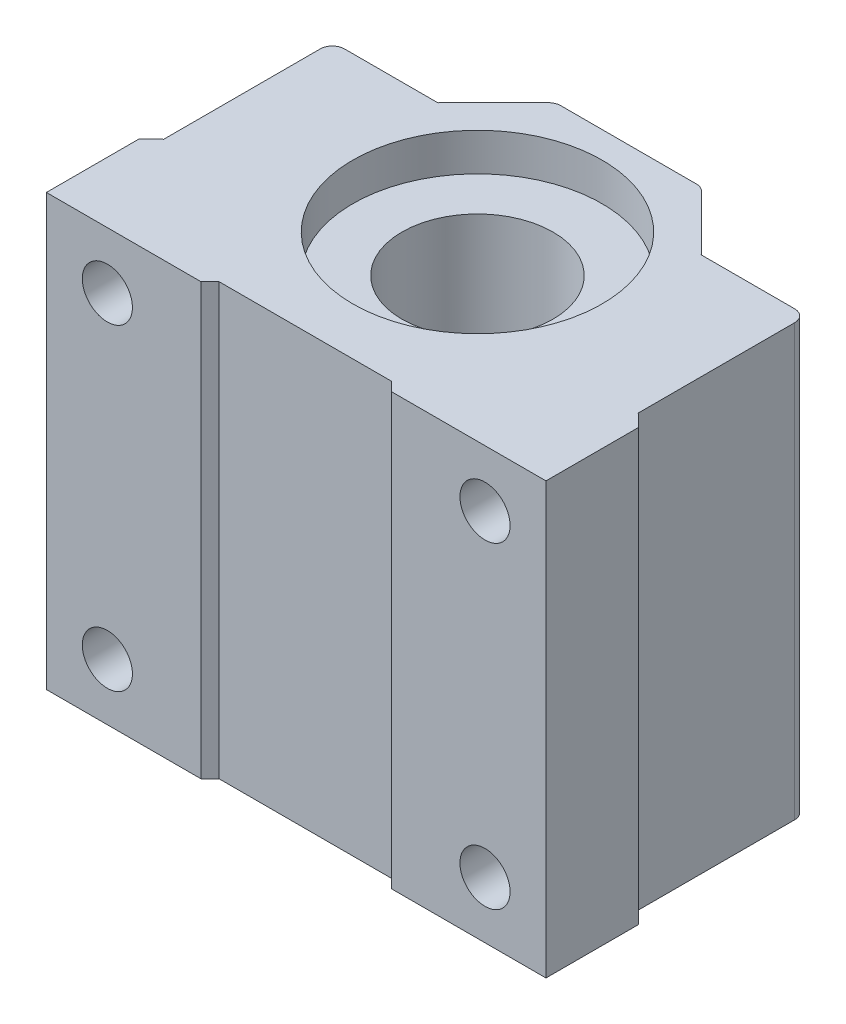
SolidWorks part; units mm, degrees
material "6061 Alloy"
ref_plane "Front Plane" through (0, 0, 0) normal (0, 0, 1) x (1, 0, 0)
ref_plane "Top Plane" through (0, 0, 0) normal (0, 1, 0) x (1, 0, 0)
ref_plane "Right Plane" through (0, 0, 0) normal (1, 0, 0) x (0, 0, -1)
sketch "Sketch1" plane through (0, 0, 0) normal (0, 1, 0) x (1, 0, 0)
  line L0 (0, -13.97) -> (0, -5.194) construction
  line L1 (-21, -13.97) -> (-6.985, -13.97)
  line L2 (-21, -13.97) -> (-21, -5.194)
  line L4 (21, -13.97) -> (21, -5.194)
  line L5 (-21, -13.97) -> (13.5468, 9.0118) construction
  line L6 (19.939, -5.194) -> (21, -5.194)
  line L7 (-21, -5.194) -> (-19.939, -5.194)
  line L8 (11.049, 9.0118) -> (19.939, 9.0118)
  line L9 (19.939, -5.194) -> (19.939, 9.0118)
  line L10 (-19.939, -5.194) -> (-19.939, 9.0118)
  line L11 (0, -13.97) -> (0, 9.0118) construction
  line L12 (-19.939, 9.0118) -> (-11.049, 9.0118)
  line L13 (11.049, 13.97) -> (-11.049, 13.97)
  line L14 (11.049, 13.97) -> (11.049, 9.0118)
  line L15 (-11.049, 13.97) -> (-11.049, 9.0118)
  line L16 (-13.5468, 9.0118) -> (21, -13.97) construction
  line L17 (0, -13.97) -> (0, -13.208) construction
  line L18 (-6.985, -13.208) -> (6.985, -13.208)
  line L19 (6.985, -13.208) -> (6.985, -13.97)
  line L20 (-6.985, -13.208) -> (-6.985, -13.97)
  line L21 (6.985, -13.97) -> (21, -13.97)
  line L22 (0, 0) -> (0, 1.27) construction
  circle A0 centre (0, 1.27) radius 6.35
  point P0 (0, 0)
  point P11 (0, -5.194)
  point P14 (-13.8734, -5.194)
  point P20 (0, 9.0118)
  point P23 (0, 13.97)
  point P26 (0, -13.208)
  dimension "D1" = 42
extrude "Boss-Extrude1" add sketch "Sketch1" along normal blind 36.195
chamfer "Chamfer1" distance 4.92 angle 45 2 edges at (11.049, 18.0975, -13.97) (-11.049, 18.0975, -13.97)
chamfer "Chamfer2" distance 1.016 angle 45 4 edges at (6.985, 18.0975, 13.97) (-6.985, 18.0975, 13.97) (-21, 18.0975, 5.194) (21, 18.0975, 5.194)
fillet "Fillet1" radius 1.016 4 edges at (-19.939, 18.0975, -9.0118) (-6.129, 18.0975, -13.97) (6.129, 18.0975, -13.97) (19.939, 18.0975, -9.0118)
sketch "Sketch2" plane through (0, 36.195, 0) normal (0, 1, 0) x (1, 0, 0)
  circle A0 centre (0, 1.27) radius 10.4775
  dimension "D1" = 20.955
extrude "Cut-Extrude1" cut sketch "Sketch2" against normal blind 3.175
sketch "Sketch3" plane through (0, 0, 0) normal (0, -1, 0) x (1, 0, 0)
  circle A0 centre (0, -1.27) radius 10.4775
  dimension "D1" = 20.955
extrude "Cut-Extrude2" cut sketch "Sketch3" against normal blind 3.175
sketch "Sketch4" plane through (0, 0, -9.0118) normal (0, 0, -1) x (-1, 0, 0)
  line L0 (-15.875, 4.7625) -> (-15.875, 31.4325) construction
  line L1 (15.875, 31.4325) -> (15.875, 4.7625) construction
  line L3 (15.875, 18.0975) -> (-15.875, 18.0975) construction
  circle A0 centre (-15.875, 4.7625) radius 2.1082
  circle A1 centre (-15.875, 31.4325) radius 2.1082
  circle A2 centre (15.875, 31.4325) radius 2.1082
  circle A3 centre (15.875, 4.7625) radius 2.1082
  point P5 (-15.875, 18.0975)
  point P8 (15.875, 18.0975)
  point P11 (0, 18.0975)
  dimension "D4" = 4.2164
  dimension "D5" = 4.2164
  dimension "D6" = 4.2164
  dimension "D7" = 4.2164
  dimension "D1" = 31.75
  dimension "D2" = 26.67
  dimension "D3" = 26.67
extrude "Cut-Extrude3" cut sketch "Sketch4" against normal blind 29.337
chamfer "Chamfer3" distance 1.016 angle 45 4 edges at (-17.9832, 4.7625, -9.0118) (-17.9832, 31.4325, -9.0118) (13.7668, 31.4325, -9.0118) (13.7668, 4.7625, -9.0118)
